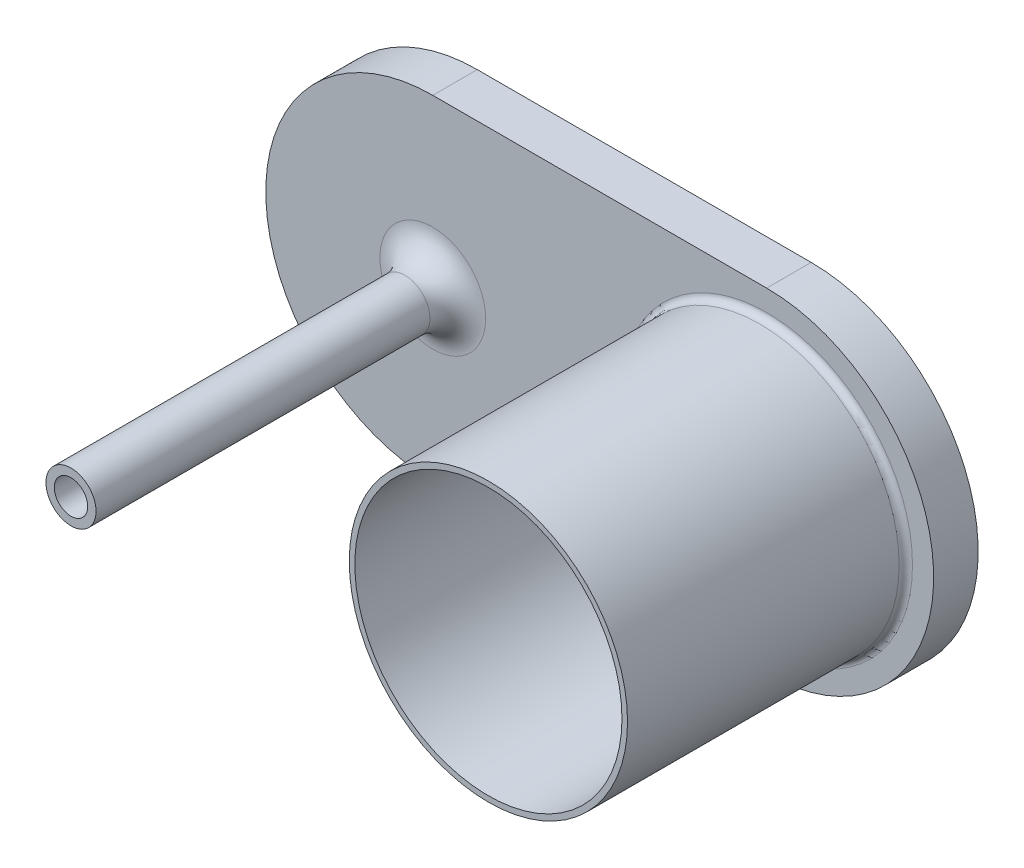
SolidWorks part; units mm, degrees
ref_plane "Front Plane" through (0, 0, 0) normal (0, 0, 1) x (1, 0, 0)
ref_plane "Top Plane" through (0, 0, 0) normal (0, 1, 0) x (1, 0, 0)
ref_plane "Right Plane" through (0, 0, 0) normal (1, 0, 0) x (0, 0, -1)
sketch "Sketch1" plane through (0, 0, 0) normal (0, 0, 1) x (1, 0, 0)
  line L0 (-30, 0) -> (30, 0) construction
  line L1 (55, 0) -> (-55, 0) construction
  line L2 (-30, 30) -> (30, 30)
  line L3 (-30, -30) -> (30, -30)
  arc A0 (-30, 30) -> (-30, -30) centre (-30, 0) ccw
  arc A1 (30, -30) -> (30, 30) centre (30, 0) ccw
  point P5 (0, 0)
  dimension "D1" = 30
  dimension "D2" = 60
  dimension "D3" = 0
extrude "Boss-Extrude1" add sketch "Sketch1" along normal blind 8
ref_plane "Plane1" through (0, 0, 0) normal (0, 1, 0) x (1, 0, 0)
sketch "Sketch2" plane through (0, 0, 0) normal (0, 1, 0) x (1, 0, 0)
  line L0 (-30, -4) -> (30, -4) construction
  line L1 (-30, -8) -> (-30, 0) construction
  line L2 (-30, -5.5) -> (30, -5.5)
  line L3 (-30, -5.5) -> (-30, -2.5)
  line L4 (-30, -2.5) -> (30, -2.5)
  line L5 (30, -5.5) -> (30, -2.5)
  line L6 (30, -8) -> (30, 0) construction
  line L7 (30, -5.5) -> (30, -7.9993) construction
  line L8 (-30, -5.5) -> (-30, -7.9993) construction
  dimension "D1" = 4
  dimension "D2" = 1.5
  dimension "D3" = 1.5
  dimension "D4" = 2.4993
extrude "Cut-Extrude1" cut sketch "Sketch2" against normal mid plane 8
sketch "Sketch3" plane through (0, 0, 8) normal (0, 0, 1) x (1, 0, 0)
  line L0 (-30, 0) -> (30, 0) construction
  circle A0 centre (30, 0) radius 4
  circle A1 centre (-30, 0) radius 3
  dimension "D1" = 8
  dimension "D2" = 6
extrude "Cut-Extrude3" cut sketch "Sketch3" against normal blind 5.5
sketch "Sketch4" plane through (0, 0, 8) normal (0, 0, 1) x (1, 0, 0)
  circle A0 centre (-30, 0) radius 4.5
  circle A2 centre (-30, 0) radius 3
  dimension "D1" = 9
  dimension "D2" = 6
extrude "Boss-Extrude3" add sketch "Sketch4" along normal blind 65
sketch "Sketch6" plane through (0, 0, 8) normal (0, 0, 1) x (1, 0, 0)
  line L0 (-30, 0) -> (30, 0) construction
  line L1 (4.4, 0) -> (-4.4, 0) construction
  circle A0 centre (30, 0) radius 25
  circle A1 centre (30, 0) radius 24
  dimension "D1" = 50
  dimension "D2" = 48
extrude "Boss-Extrude4" add sketch "Sketch6" along normal blind 50
fillet "Fillet1" radius 5 1 edges at (-25.5, 0, 8)
sketch "Sketch7" plane through (0, 0, 8) normal (0, 0, 1) x (1, 0, 0)
  line L1 (30, 4) -> (-30, 4) construction
  line L4 (30, 4) -> (10, 4)
  line L5 (10, 4) -> (10, -4)
  line L6 (10, -4) -> (30, -4)
  circle A2 centre (30, 0) radius 4 construction
  arc A3 (30, -4) -> (30, 4) centre (30, 0) ccw construction
  arc A4 (30, -4) -> (30, 4) centre (30, 0) cw
  dimension "D3" = 4
  dimension "D1" = 20
  dimension "D2" = 8
extrude "Cut-Extrude4" cut sketch "Sketch7" against normal blind 3
fillet "Fillet2" radius 1.2 1 edges at (55, 0, 8)
fillet "Fillet3" radius 4 1 edges at (54, 0, 8)
equation "\"lin\"=45"
